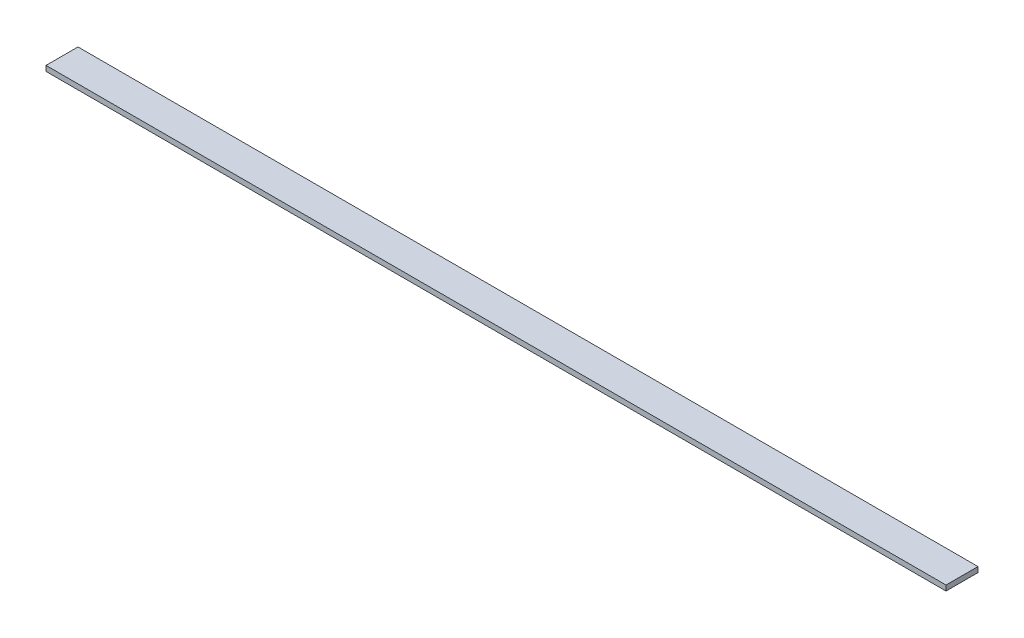
SolidWorks part; units mm, degrees
material "XPS 2.3lb"
ref_plane "Front Plane" through (0, 0, 0) normal (0, 0, 1) x (1, 0, 0)
ref_plane "Top Plane" through (0, 0, 0) normal (0, 1, 0) x (1, 0, 0)
ref_plane "Right Plane" through (0, 0, 0) normal (1, 0, 0) x (0, 0, -1)
sketch "Sketch1" plane through (0, 0, 0) normal (0, 1, 0) x (1, 0, 0)
  line L2 (0, 0) -> (0, -62.2808)
  line L5 (0, 0) -> (-1752.6, 0)
  line L6 (-1752.6, 0) -> (-1752.6, -62.2808)
  line L7 (-1752.6, -62.2808) -> (0, -62.2808)
  dimension "D1" = 62.2808
  dimension "D2" = 1752.6
extrude "Boss-Extrude" add sketch "Sketch1" along normal mid plane 10.2108
ref_point "Point1"
ref_point "Point2"
ref_axis "Axis1" through (-1752.6, 0, 31.1404) along (1, 0, 0)
